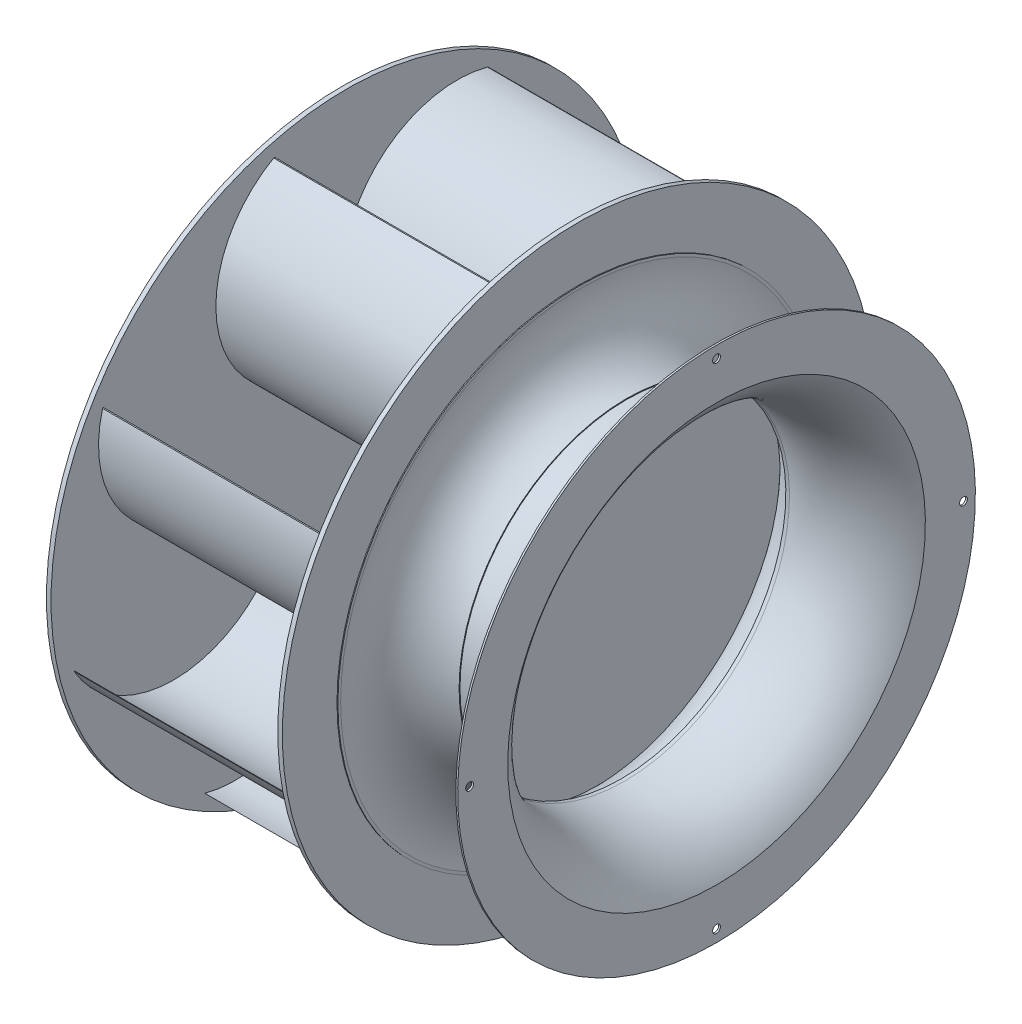
SolidWorks part; units mm, degrees
ref_plane "Front Plane" through (0, 0, 0) normal (0, 0, 1) x (1, 0, 0)
ref_plane "Top Plane" through (0, 0, 0) normal (0, 1, 0) x (1, 0, 0)
ref_plane "Right Plane" through (0, 0, 0) normal (1, 0, 0) x (0, 0, -1)
sketch "Sketch1" plane through (0, 0, 0) normal (0, 0, 1) x (1, 0, 0)
  line L0 (0, 0) -> (831.9083, 0) construction
  line L1 (0, 0) -> (0, 109)
  line L2 (5, 114) -> (70, 114)
  line L3 (70, 114) -> (70, 138)
  line L4 (70, 138) -> (90, 138)
  line L5 (90, 138) -> (90, 98)
  line L6 (90, 98) -> (95, 98)
  line L7 (95, 98) -> (95, 133)
  line L8 (95, 133) -> (105, 133)
  line L9 (105, 133) -> (105, 98)
  line L10 (105, 98) -> (129, 98)
  line L11 (129, 98) -> (129, 0)
  line L12 (129, 0) -> (0, 0)
  arc A0 (5, 114) -> (0, 109) centre (5, 109) ccw
  point P16 (0, 114)
  dimension "D10" = 5
  dimension "D1" = 114
  dimension "D2" = 24
  dimension "D3" = 70
  dimension "D4" = 40
  dimension "D5" = 35
  dimension "D6" = 5
  dimension "D7" = 20
  dimension "D8" = 10
  dimension "D9" = 59
revolve "Revolve1" add sketch "Sketch1" angle 360 about L0
sketch "Sketch2" plane through (129, 0, 0) normal (1, 0, 0) x (0, 0, -1)
  circle A0 centre (0, 0) radius 322
  dimension "D1" = 644
extrude "Extrude1" add sketch "Sketch2" along normal blind 5
sketch "Sketch9" plane through (129, 0, 0) normal (-1, 0, 0) x (0, 0, 1)
  circle A0 centre (0, 0) radius 317
  circle A1 centre (0, 0) radius 100
  circle A2 centre (0, 0) radius 322 construction
  dimension "D1" = 5
  dimension "D2" = 200
extrude "Extrude7" cut sketch "Sketch9" against normal blind 3
ref_plane "Plane1" through (381, 0, 0) normal (1, 0, 0) x (0, 0, -1)
sketch "Sketch3" plane through (381, 0, 0) normal (1, 0, 0) x (0, 0, -1)
  circle A0 centre (0, 0) radius 322
  dimension "D1" = 644
extrude "Extrude2" add sketch "Sketch3" along normal blind 5 separate body
sketch "Sketch4" plane through (134, 0, 0) normal (1, 0, 0) x (0, 0, -1)
  line L0 (0, 0) -> (0, 307) construction
  line L1 (0, 0) -> (161, 278.8602) construction
  line L2 (0, 112.5) -> (0.866, 112)
  line L3 (153.5, 265.8698) -> (154.366, 265.3698)
  circle A0 centre (0, 0) radius 307 construction
  circle A1 centre (0, 0) radius 322 construction
  circle A2 centre (0, 0) radius 112.5 construction
  arc A3 (0, 112.5) -> (153.5, 265.8698) centre (120.6282, 145.2694) cw
  arc A4 (0.866, 112) -> (154.366, 265.3698) centre (121.4942, 144.7694) cw
  dimension "D1" = 15
  dimension "D2" = 225
  dimension "D6" = 125
  dimension "D7" = 125
  dimension "D3" = 30
  dimension "D4" = 60
  dimension "D5" = 1
extrude "Extrude3" add sketch "Sketch4" along normal up to surface (252 mm away) up to face at (386, 0, -322)
ref_axis "Axis1" through (253.5503, 0, 0) along (-1, 0, 0)
pattern_circular "CirPattern1" count 8 over 360 about axis through (253.5503, 0, 0) along (-1, 0, 0) of "Extrude3"
sketch "Sketch5" plane through (0, 0, 0) normal (0, 0, 1) x (1, 0, 0)
  line L0 (0, 0) -> (527.2916, 0) construction
  line L1 (253.5503, 0) -> (75.411, 0) construction
  line L2 (386, 262.5) -> (387, 262.5)
  line L3 (387, 262.5) -> (387, 259.5)
  line L4 (386, 262.5) -> (386, 259.5)
  line L5 (439, 182.5) -> (439, 181.5)
  line L6 (70, 138) -> (70, -138) construction
  line L7 (386, -322) -> (386, 322) construction
  arc A0 (387, 259.5) -> (439, 182.5) centre (456.3934, 250.3046) ccw
  arc A1 (386, 259.5) -> (439, 181.5) centre (455.2932, 249.5774) ccw
  dimension "D7" = 70
  dimension "D8" = 70
  dimension "D1" = 181.5
  dimension "D2" = 1
  dimension "D3" = 1
  dimension "D4" = 3
  dimension "D5" = 262.5
  dimension "D6" = 369
revolve "Revolve2" add sketch "Sketch5" angle 360 about L0
ref_plane "Plane3" through (537, 0, 0) normal (1, 0, 0) x (0, 0, -1)
sketch "Sketch6" plane through (0, 0, 0) normal (0, 0, 1) x (1, 0, 0)
  line L0 (537, 282) -> (535, 282)
  line L1 (537, -251.35) -> (537, 251.35) construction
  line L2 (535, 282) -> (535, 227.5)
  line L3 (0, 0) -> (615.1417, 0) construction
  line L4 (0, 114) -> (0, -114) construction
  line L5 (253.5503, 0) -> (75.411, 0) construction
  line L6 (537, 282) -> (537, 227.5)
  line L7 (433, 181.5) -> (437, 181.5)
  line L8 (433, 181.5) -> (433, 179.5)
  line L9 (433, 179.5) -> (437, 179.5)
  arc A0 (437, 181.5) -> (535, 227.5) centre (450.2724, 280.6153) ccw
  arc A1 (437, 179.5) -> (537, 227.5) centre (450.9922, 278.5163) ccw
  dimension "D7" = 100
  dimension "D8" = 100
  dimension "D1" = 282
  dimension "D2" = 2
  dimension "D3" = 227.5
  dimension "D4" = 104
  dimension "D5" = 181.5
  dimension "D6" = 4
revolve "Revolve3" add sketch "Sketch6" angle 360 about L3
sketch "Sketch7" plane through (537, 0, 0) normal (1, 0, 0) x (0, 0, -1)
  line L0 (0, 0) -> (0, 269) construction
  circle A0 centre (0, 0) radius 269 construction
  circle A1 centre (0, 269) radius 4.25
  dimension "D1" = 538
  dimension "D2" = 8.5
extrude "Extrude5" cut sketch "Sketch7" against normal blind 5
pattern_circular "CirPattern2" count 4 over 360 about axis through (253.5503, 0, 0) along (-1, 0, 0) of "Extrude5"
sketch "Sketch8" plane through (0, 0, 0) normal (1, 0, 0) x (0, 0, -1)
  line L0 (0, 0) -> (0, 126) construction
  circle A0 centre (0, 0) radius 126 construction
  circle A1 centre (0, 126) radius 5
  dimension "D1" = 252
  dimension "D2" = 10
extrude "Extrude6" cut sketch "Sketch8" along normal up to surface (90 mm away) up to face at (90, 0, 138)
pattern_circular "CirPattern3" count 8 over 360 about axis through (253.5503, 0, 0) along (-1, 0, 0) of "Extrude6"
